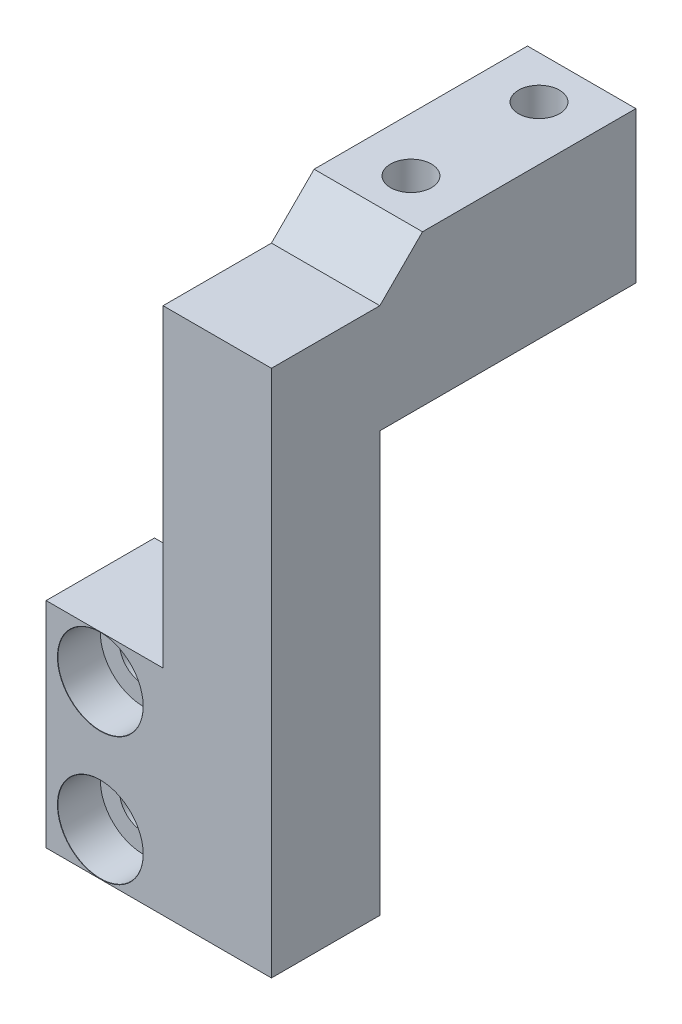
SolidWorks part; units mm, degrees
ref_plane "Front Plane" through (0, 0, 0) normal (0, 0, 1) x (1, 0, 0)
ref_plane "Top Plane" through (0, 0, 0) normal (0, 1, 0) x (1, 0, 0)
ref_plane "Right Plane" through (0, 0, 0) normal (1, 0, 0) x (0, 0, -1)
sketch "Sketch2" plane through (0, 0, 0) normal (0, 1, 0) x (1, 0, 0)
  line L1 (-6.35, -42) -> (6.35, -42)
  line L2 (-6.35, -42) -> (-6.35, 42)
  line L3 (-6.35, 42) -> (6.35, 42)
  line L4 (6.35, -42) -> (6.35, 42)
  line L5 (-6.35, -42) -> (6.35, 42) construction
  line L6 (-6.35, 42) -> (6.35, -42) construction
  point P0 (0, 0)
  dimension "D1" = 84
  dimension "D2" = 12.7
extrude "Boss-Extrude1" add sketch "Sketch2" along normal blind 12.7
sketch "Sketch5" plane through (0, 12.7, 0) normal (0, 1, 0) x (1, 0, 0)
  line L0 (6.35, 42) -> (-6.35, 42) construction
  line L2 (-6.35, 42) -> (6.35, 42)
  line L3 (-6.35, 42) -> (-6.35, 17)
  line L4 (-6.35, 17) -> (6.35, 17)
  line L5 (6.35, 42) -> (6.35, 17)
  point P7 (0, 17)
  dimension "D1" = 12.7
  dimension "D2" = 25
extrude "Boss-Extrude2" add sketch "Sketch5" along normal blind 5
hole_wizard "CBORE for M4 SHCS1" positions "Sketch3" profile "Sketch4" counterbore size "M4" standard "ANSI Metric" end condition through all
sketch "Sketch3" plane through (0, 0, 0) normal (0, -1, 0) x (-1, 0, 0)
  line L0 (0, 37) -> (0, 22) construction
  line L3 (-6.35, 42) -> (6.35, 42) construction
  point P0 (0, 37)
  point P2 (0, 22)
  dimension "D2" = 5
  dimension "D1" = 15
sketch "Sketch4" plane through (0, 0, -37) normal (1, 0, 0) x (0, 0, -1)
  line L0 (0, 0) -> (0, 17.7)
  line L1 (0, 17.7) -> (2.4, 17.7)
  line L3 (2.4, 17.7) -> (2.4, 4)
  line L4 (4, 4) -> (2.4, 4)
  line L5 (4, 4) -> (4, 0.021)
  line L6 (4, 0.021) -> (4.025, 0)
  line L7 (4.025, 0) -> (0, 0)
  line L8 (-4, 0.021) -> (-4.025, 0) construction
  line L11 (0, -6.35) -> (0, 107.95) construction
  dimension "Thru Hole Dia." = 4.8
  dimension "Thru Hole Depth" = 17.7
  dimension "C'Bore Dia." = 8
  dimension "C'Bore Depth" = 4
  dimension "Near C'Sink Dia." = 8.05
  dimension "Near C'Sink Angle" = 100
chamfer "Chamfer1" distance 5 angle 45 1 edges at (0, 12.7, -17)
sketch "Sketch6" plane through (6.35, 0, 0) normal (1, 0, 0) x (0, 0, -1)
  line L0 (-42, 0) -> (42, 0) construction
  line L1 (-42, 12.7) -> (-0.7, 12.7)
  line L2 (-42, 12.7) -> (-42, 0)
  line L3 (-42, 0) -> (-0.7, 0)
  line L4 (-0.7, 12.7) -> (-0.7, 0)
  line L5 (12, 12.7) -> (12, 0) construction
  dimension "D1" = 12.7
extrude "Cut-Extrude1" cut sketch "Sketch6" against normal through all
sketch "Sketch7" plane through (0, 0, 0) normal (0, -1, 0) x (-1, 0, 0)
  line L0 (-6.35, -0.7) -> (-6.35, 42) construction
  line L1 (6.35, -0.7) -> (-6.35, -0.7)
  line L2 (6.35, -0.7) -> (6.35, 12)
  line L3 (6.35, 12) -> (-6.35, 12)
  line L4 (-6.35, -0.7) -> (-6.35, 12)
  dimension "D1" = 12.7
extrude "Boss-Extrude3" add sketch "Sketch7" along normal blind 49.17
sketch "Sketch9" plane through (-6.35, 0, 0) normal (1, 0, 0) x (0, 0, -1)
  line L1 (-0.7, -49.17) -> (12, -49.17)
  line L2 (-0.7, -49.17) -> (-0.7, -24.07)
  line L3 (-0.7, -24.07) -> (12, -24.07)
  line L4 (12, -49.17) -> (12, -24.07)
  line L5 (12, -49.17) -> (12, 0) construction
  dimension "D1" = 25.1
extrude "Boss-Extrude4" add sketch "Sketch9" against normal blind 13.7
hole_wizard "CBORE for M5 SHCS2" positions "Sketch13" profile "Sketch14" counterbore size "M5" standard "ANSI Metric" end condition through all
sketch "Sketch13" plane through (0, 0, 0.7) normal (0, 0, 1) x (1, 0, 0)
  line L0 (-13.7, -29.12) -> (-13.7, -44.12) construction
  line L2 (-20.05, -24.07) -> (-20.05, -49.17) construction
  point P0 (-13.7, -29.12)
  point P2 (-13.7, -44.12)
  point P11 (-20.05, -36.62)
  point P12 (-13.7, -36.62)
  dimension "D1" = 6.35
  dimension "D2" = 15
sketch "Sketch14" plane through (-13.7, -29.12, 0.7) normal (1, 0, 0) x (0, -1, 0)
  line L0 (0, 0) -> (0, 42.7)
  line L1 (0, 42.7) -> (2.75, 42.7)
  line L3 (2.75, 42.7) -> (2.75, 5)
  line L4 (5, 5) -> (2.75, 5)
  line L5 (5, 5) -> (5, 0.025)
  line L6 (5, 0.025) -> (5.025, 0)
  line L7 (5.025, 0) -> (0, 0)
  line L8 (-5, 0.025) -> (-5.025, 0) construction
  line L11 (0, -6.35) -> (0, 107.95) construction
  dimension "Thru Hole Dia." = 5.5
  dimension "Thru Hole Depth" = 42.7
  dimension "C'Bore Dia." = 10
  dimension "C'Bore Depth" = 5
  dimension "Near C'Sink Dia." = 10.05
  dimension "Near C'Sink Angle" = 90
